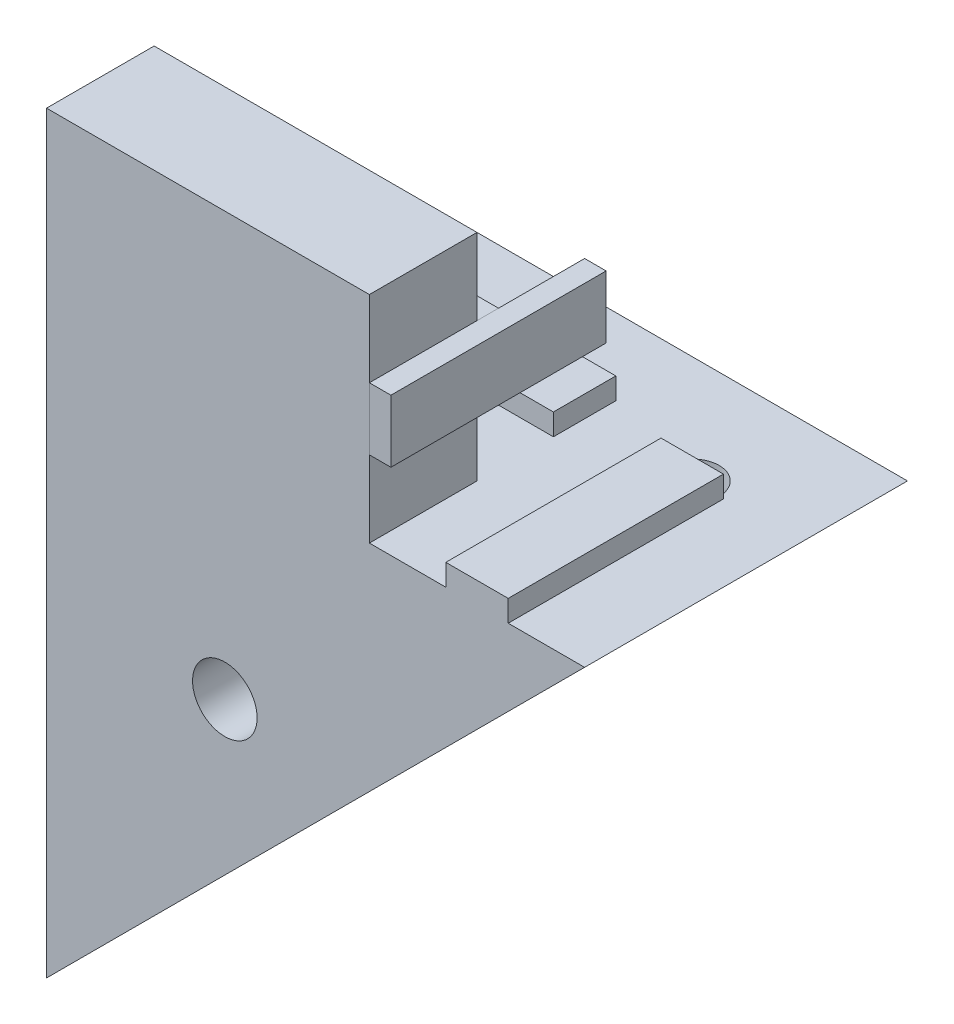
SolidWorks part; units mm, degrees
ref_plane "Front Plane" through (0, 0, 0) normal (0, 0, 1) x (1, 0, 0)
ref_plane "Top Plane" through (0, 0, 0) normal (0, 1, 0) x (1, 0, 0)
ref_plane "Right Plane" through (0, 0, 0) normal (1, 0, 0) x (0, 0, -1)
ref_plane "FrontPlane+10mm" through (0, 0, 10) normal (0, 0, 1) x (1, 0, 0)
sketch "Sketch1" plane through (0, 0, 0) normal (0, 0, 1) x (1, 0, 0)
  line L0 (-290, 0) -> (-10, 0) construction
  line L1 (0, 0) -> (-90, -90) construction
  line L2 (-10, 0) -> (0, 0) construction
  line L3 (-10, 0) -> (-10, 10) construction
  line L4 (-10, 10) -> (0, 10) construction
  line L5 (0, 0) -> (0, 10) construction
  line L6 (-90, -90) -> (-210, -90) construction
  line L7 (-300, 10) -> (-290, 10) construction
  line L8 (-300, 10) -> (-300, 0) construction
  line L9 (0, 0) -> (-10, 0)
  line L10 (-290, 10) -> (-290, 0) construction
  line L11 (-210, -90) -> (-300, 0) construction
  line L12 (-87.4264, -73.2843) -> (-16.7157, -2.5736) construction
  line L13 (-100, -80) -> (-90, -80) construction
  line L14 (-100, -80) -> (-100, -90) construction
  line L15 (-10, 0) -> (-10, 10)
  line L16 (-90, -80) -> (-90, -90) construction
  line L17 (-16.7157, -2.5736) -> (-9.6447, -9.6447) construction
  line L18 (-87.4264, -73.2843) -> (-80.3553, -80.3553) construction
  line L19 (-16.7157, -2.5736) -> (0, 0) construction
  line L20 (-87.4264, -73.2843) -> (-90, -90) construction
  line L21 (-10, 10) -> (-25, 10)
  line L22 (0, 0) -> (-9.6447, -9.6447)
  line L23 (-9.6447, -9.6447) -> (-16.7157, -2.5736)
  line L24 (-16.7157, -2.5736) -> (-25, -10.8579)
  line L25 (-25, -10.8579) -> (-25, 10)
  dimension "D1" = 10
  dimension "D2" = 10
  dimension "D3" = 300
  dimension "D4" = 10
  dimension "D5" = 120
  dimension "D6" = 135
  dimension "D7" = 45
  dimension "D8" = 45
  dimension "D9" = 127.2792
  dimension "D10" = 10
  dimension "D11" = 10
  dimension "D12" = 10
  dimension "D13" = 100
  dimension "D14" = 25
extrude "Main" add sketch "Sketch1" along normal blind 15
sketch "Sketch4" plane through (0, 0, 0) normal (0, 0, -1) x (-1, 0, 0)
  line L1 (10, 0) -> (25, 0)
  line L2 (10, 0) -> (10, 10)
  line L3 (10, 10) -> (25, 10)
  line L4 (25, 0) -> (25, 10)
extrude "Cut-Extrude2" cut sketch "Sketch4" against normal blind 10
sketch "Sketch2" plane through (0, 0, 10) normal (0, 0, -1) x (-1, 0, 0)
  line L0 (10, 0) -> (10, 10) construction
  line L1 (10, 6.45) -> (25, 6.45)
  line L2 (10, 6.45) -> (10, 3.55)
  line L3 (10, 3.55) -> (25, 3.55)
  line L4 (25, 6.45) -> (25, 3.55)
  line L5 (25, 0) -> (25, -10.8579) construction
  line L6 (10, 10) -> (25, 10) construction
  dimension "D1" = 3.55
  dimension "D2" = 2.9
extrude "Boss-Extrude3" add sketch "Sketch2" along normal blind 1
sketch "Sketch5" plane through (-7.0711, 7.0711, 0) normal (0.7071, -0.7071, 0) x (0, 0, -1)
  line L0 (-15, -25.3553) -> (0, -25.3553) construction
  line L1 (-3.55, -25.3553) -> (-6.45, -25.3553)
  line L2 (-3.55, -25.3553) -> (-3.55, -13.6396)
  line L3 (-3.55, -13.6396) -> (-6.45, -13.6396)
  line L4 (-6.45, -25.3553) -> (-6.45, -13.6396)
  line L5 (-15, -13.6396) -> (0, -13.6396) construction
  line L6 (0, -25.3553) -> (0, -13.6396) construction
  dimension "D1" = 3.55
  dimension "D2" = 2.9
extrude "Boss-Extrude4" add sketch "Sketch5" along normal blind 1
sketch "Sketch6" plane through (0, 0, 10) normal (0, 0, 1) x (1, 0, 0)
  line L0 (-25, -10.8579) -> (-16.7157, -2.5736)
  line L1 (-16.7157, -2.5736) -> (-9.6447, -9.6447)
  line L2 (-9.6447, -9.6447) -> (-25, -25)
  line L3 (-25, -10.8579) -> (-25, -25)
  line L4 (-13.1802, -6.1091) -> (-20.2513, -13.1802) construction
  circle A0 centre (-16.7157, -9.6447) radius 1.5
  point P11 (-25, -24.9823)
  point P12 (-16.6825, -9.6775)
  point P13 (-16.7157, -9.6447)
  point P14 (0, 0)
  dimension "D1" = 3
  dimension "D2" = 21.7157
  dimension "D3" = 14.1421
  dimension "D4" = 5
extrude "Boss-Extrude5" add sketch "Sketch6" along normal blind 5
sketch "Sketch7" plane through (0, 0, 10) normal (0, 0, -1) x (-1, 0, 0)
  line L0 (14.2055, -5.0838) -> (25, -15.8783)
  line L1 (25, -10.8579) -> (25, -25) construction
  line L3 (25, -15.8783) -> (25, -19.9795)
  line L4 (25, -19.9795) -> (12.1549, -7.1344)
  line L5 (12.1549, -7.1344) -> (14.2055, -5.0838)
  line L7 (9.6447, -9.6447) -> (16.7157, -2.5736) construction
  line L8 (16.7157, -2.5736) -> (9.6447, -9.6447) construction
  line L10 (25, -25) -> (0, 0) construction
  point P2 (25, -20.0105)
  point P8 (15.2239, -13.4218)
  point P9 (25, -15.8836)
  dimension "D1" = 2.9
  dimension "D2" = 3.55
extrude "Boss-Extrude6" add sketch "Sketch7" along normal blind 1
sketch "Sketch8" plane through (0, 0, 0) normal (0, 1, 0) x (1, 0, 0)
  line L0 (0, -15) -> (-10, -15) construction
  line L1 (-3.55, -15) -> (-6.45, -15)
  line L2 (-3.55, -15) -> (-3.55, -5)
  line L3 (-3.55, -5) -> (-6.45, -5)
  line L4 (-6.45, -15) -> (-6.45, -5)
  line L5 (0, -15) -> (0, 0) construction
  dimension "D1" = 3.55
  dimension "D2" = 2.9
  dimension "D3" = 10
extrude "Boss-Extrude7" add sketch "Sketch8" along normal blind 1
sketch "Sketch9" plane through (0, 0, 15) normal (0, 0, 1) x (1, 0, 0)
  line L0 (-10, 0) -> (-10, 10) construction
  line L1 (-10, 6.45) -> (-9, 6.45)
  line L2 (-10, 6.45) -> (-10, 3.55)
  line L3 (-10, 3.55) -> (-9, 3.55)
  line L4 (-9, 6.45) -> (-9, 3.55)
  line L5 (-10, 10) -> (-25, 10) construction
  dimension "D1" = 1
  dimension "D2" = 3.55
  dimension "D3" = 2.9
extrude "Boss-Extrude8" add sketch "Sketch9" against normal blind 10 separate body
sketch "Sketch11" plane through (0, 0, 0) normal (0, 1, 0) x (1, 0, 0)
  line L0 (0, -15) -> (0, 0) construction
  line L1 (0, 0) -> (-25, 0) construction
  circle A0 centre (-5, -5) radius 1.25
  dimension "D1" = 2.5
  dimension "D2" = 5
  dimension "D3" = 5
extrude "Cut-Extrude4" cut sketch "Sketch11" against normal through all
sketch "Sketch12" plane through (0, 0, 15) normal (0, 0, 1) x (1, 0, 0)
  circle A0 centre (-16.7157, -9.6447) radius 1.5
  arc A1 (-15.4189, -10.3984) -> (-17.4695, -8.3478) centre (-16.7157, -9.6447) ccw construction
extrude "Cut-Extrude5" cut sketch "Sketch12" against normal through all
sketch "Sketch13" plane through (0, 0, 0) normal (0, 1, 0) x (1, 0, 0)
  line L0 (-25, -10) -> (-25, 0) construction
  line L1 (-10, -3.55) -> (-25, -3.55)
  line L2 (-10, -3.55) -> (-10, -6.45)
  line L3 (-10, -6.45) -> (-25, -6.45)
  line L4 (-25, -3.55) -> (-25, -6.45)
  line L5 (0, -15) -> (0, 0) construction
  line L6 (0, 0) -> (-25, 0) construction
  dimension "D1" = 10
  dimension "D2" = 2.9
  dimension "D3" = 3.55
extrude "Boss-Extrude9" add sketch "Sketch13" along normal blind 1
